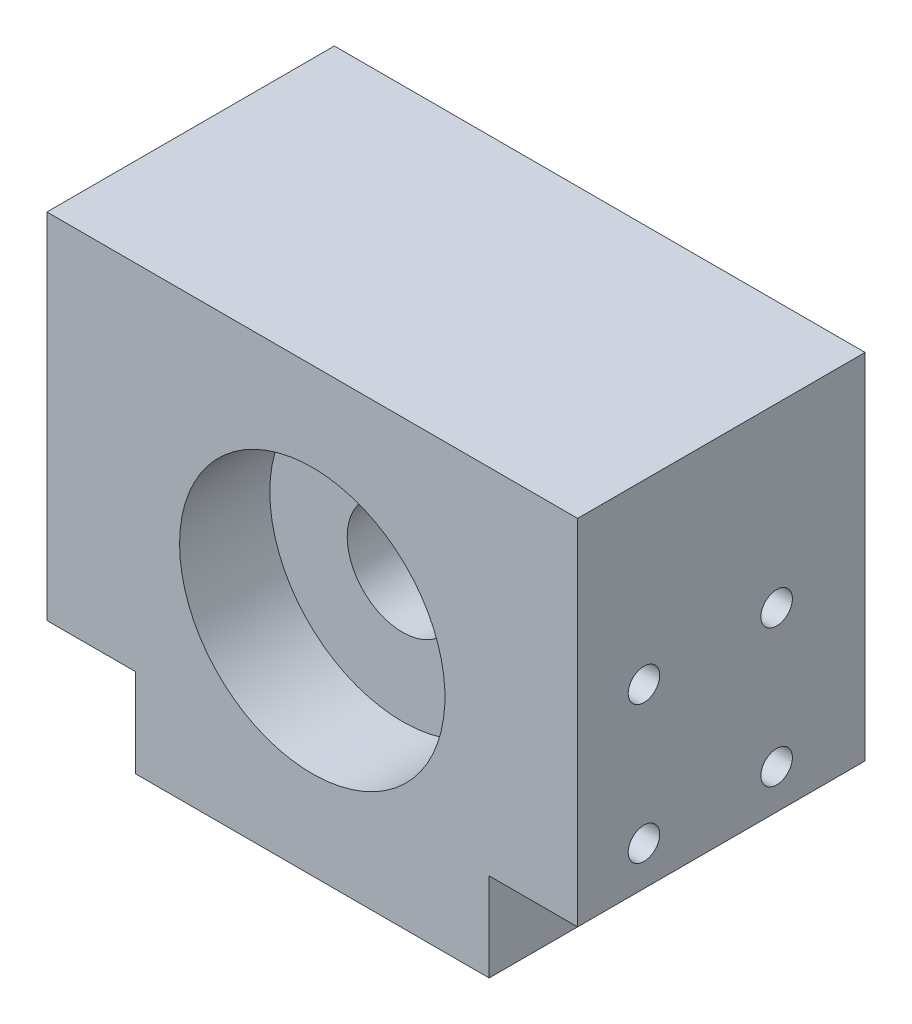
SolidWorks part; units mm, degrees
material "1060 Alloy"
ref_plane "Front" through (0, 0, 0) normal (0, 0, 1) x (1, 0, 0)
ref_plane "Top" through (0, 0, 0) normal (0, 1, 0) x (1, 0, 0)
ref_plane "Right" through (0, 0, 0) normal (1, 0, 0) x (0, 0, -1)
sketch "Sketch1" plane through (0, 0, 0) normal (0, 0, 1) x (1, 0, 0)
  line L1 (19.05, -15.875) -> (-19.05, -15.875)
  line L2 (19.05, -15.875) -> (19.05, 15.875)
  line L3 (19.05, 15.875) -> (-19.05, 15.875)
  line L4 (-19.05, -15.875) -> (-19.05, 15.875)
  line L5 (19.05, -15.875) -> (-19.05, 15.875) construction
  line L6 (19.05, 15.875) -> (-19.05, -15.875) construction
  point P0 (0, 0)
  dimension "D1" = 31.75
  dimension "D2" = 38.1
extrude "Boss-Extrude1" add sketch "Sketch1" along normal blind 20.6375
sketch "Sketch2" plane through (0, 0, 0) normal (0, 0, -1) x (-1, 0, 0)
  circle A0 centre (0, 0) radius 11.1125
  dimension "D1" = 22.225
extrude "Cut-Extrude1" cut sketch "Sketch2" against normal blind 6.985
sketch "Sketch3" plane through (0, 0, 6.985) normal (0, 0, -1) x (-1, 0, 0)
  circle A0 centre (0, 0) radius 8.255
  dimension "D1" = 16.51
extrude "Cut-Extrude2" cut sketch "Sketch3" against normal blind 2.413
sketch "Sketch4" plane through (0, 0, 9.398) normal (0, 0, -1) x (-1, 0, 0)
  circle A0 centre (0, 0) radius 3.9688
  dimension "D1" = 7.9375
extrude "Cut-Extrude3" cut sketch "Sketch4" against normal through all
sketch "Sketch6" plane through (0, 0, 9.398) normal (0, 0, -1) x (-1, 0, 0)
  circle A0 centre (0, 0) radius 9.525
  dimension "D1" = 19.05
extrude "Cut-Extrude4" cut sketch "Sketch6" against normal through all from offset 4.7625 offset against normal yes
hole_wizard "#4-40 Tapped Hole2" positions "Sketch7" profile "Sketch8" tap size "#4-40" standard "ANSI Inch"
sketch "Sketch7" plane through (-19.05, -28.277, 98.8948) normal (-1, 0, 0) x (0, 0, 1)
  point P0 (-92.5448, 31.452)
  point P1 (-83.0198, 31.452)
  point P2 (-83.0198, 21.927)
  point P3 (-92.5448, 21.927)
sketch "Sketch8" plane through (-19.05, 3.175, 6.35) normal (0, 1, 0) x (0, 0, 1)
  line L0 (0, 0) -> (0, 8.2992)
  line L1 (0, 8.2992) -> (1.1303, 7.62)
  line L2 (1.1303, 7.62) -> (1.1303, 0)
  line L5 (1.1303, 0) -> (0, 0)
  line L10 (0, 8.2992) -> (-1.1303, 7.62) construction
  line L11 (0, -6.35) -> (0, 107.95) construction
  dimension "Tap Drill Dia." = 2.2606
  dimension "Tap Drill Depth" = 7.62
  dimension "Drill Angle" = 118
cosmetic thread "Hole Thread5" parameters "D1"=5.588, "D2"=2.8448
cosmetic thread "Hole Thread6" parameters "D1"=5.588, "D2"=2.8448
cosmetic thread "Hole Thread7" parameters "D1"=5.588, "D2"=2.8448
cosmetic thread "Hole Thread8" parameters "D1"=5.588, "D2"=2.8448
hole_wizard "#4-40 Tapped Hole1" positions "Sketch11" profile "Sketch12" tap size "#4-40" standard "ANSI Inch"
sketch "Sketch11" plane through (19.05, -28.277, 98.8948) normal (1, 0, 0) x (0, 0, -1)
  point P0 (92.5448, 31.452)
  point P1 (83.0198, 31.452)
  point P2 (83.0198, 21.5728)
  point P3 (92.5448, 21.5728)
cosmetic thread "Hole Thread1" parameters "D1"=5.588, "D2"=2.8448
cosmetic thread "Hole Thread2" parameters "D1"=5.588, "D2"=2.8448
cosmetic thread "Hole Thread3" parameters "D1"=5.588, "D2"=2.8448
cosmetic thread "Hole Thread4" parameters "D1"=5.588, "D2"=2.8448
sketch "Sketch12" plane through (19.05, 3.175, 6.35) normal (0, 1, 0) x (0, 0, -1)
  line L0 (0, 0) -> (0, 8.2992)
  line L1 (0, 8.2992) -> (1.1303, 7.62)
  line L2 (1.1303, 7.62) -> (1.1303, 0)
  line L5 (1.1303, 0) -> (0, 0)
  line L10 (0, 8.2992) -> (-1.1303, 7.62) construction
  line L11 (0, -6.35) -> (0, 107.95) construction
  dimension "Tap Drill Dia." = 2.2606
  dimension "Tap Drill Depth" = 7.62
  dimension "Drill Angle" = 118
sketch "Sketch13" plane through (0, 0, 20.6375) normal (0, 0, 1) x (1, 0, 0)
  line L0 (0, 0) -> (0, 49.175) construction
  line L1 (-19.05, -9.525) -> (-12.7, -9.525)
  line L2 (-19.05, -9.525) -> (-19.05, -15.875)
  line L3 (-19.05, -15.875) -> (-12.7, -15.875)
  line L4 (-12.7, -9.525) -> (-12.7, -15.875)
  line L5 (19.05, -15.875) -> (12.7, -15.875)
  line L6 (19.05, -9.525) -> (19.05, -15.875)
  line L7 (19.05, -9.525) -> (12.7, -9.525)
  line L8 (12.7, -9.525) -> (12.7, -15.875)
  dimension "D1" = 25.4
  dimension "D2" = 6.35
extrude "Cut-Extrude5" cut sketch "Sketch13" against normal up to surface (20.6375 mm away) up to face at (-11.1125, 0, 0)
